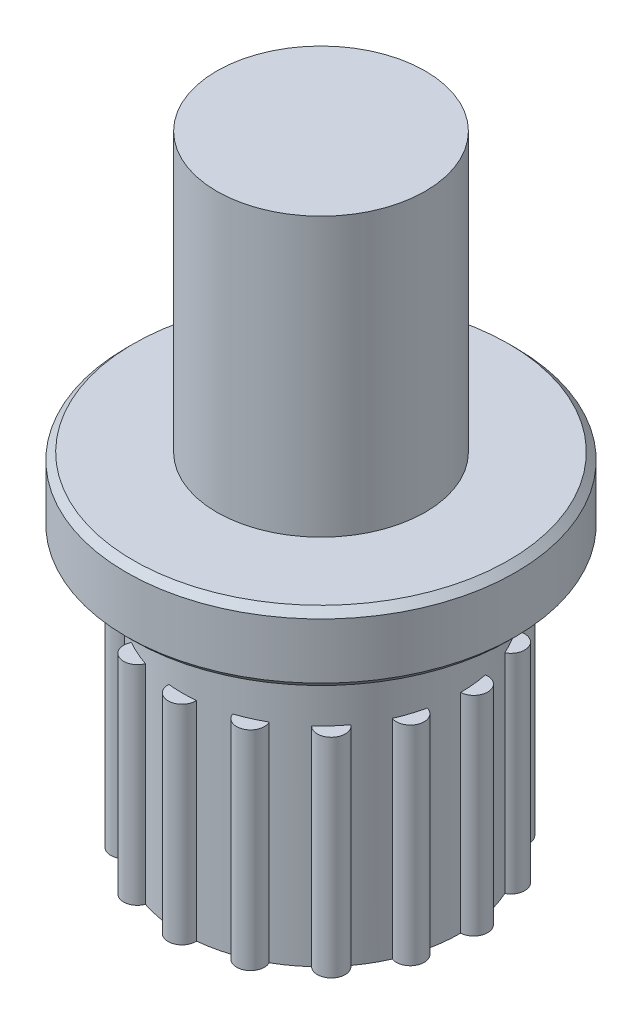
SolidWorks part; units mm, degrees
ref_plane "Front Plane" through (0, 0, 0) normal (0, 0, 1) x (1, 0, 0)
ref_plane "Top Plane" through (0, 0, 0) normal (0, 1, 0) x (1, 0, 0)
ref_plane "Right Plane" through (0, 0, 0) normal (1, 0, 0) x (0, 0, -1)
sketch "Sketch2" plane through (0, 0, 0) normal (1, 0, 0) x (0, 0, -1)
  line L0 (0, 0) -> (10, 0)
  line L1 (10, 0) -> (10, 20)
  line L2 (10, 20) -> (14, 20)
  line L3 (14, 20) -> (14, 25)
  line L4 (14, 25) -> (7.5, 25)
  line L5 (7.5, 25) -> (7.5, 45)
  line L6 (7.5, 45) -> (0, 45)
  line L7 (0, 45) -> (0, 0)
  dimension "D1" = 7.5
  dimension "D2" = 14
  dimension "D3" = 10
  dimension "D4" = 20
  dimension "D5" = 5
  dimension "D6" = 20
revolve "Revolve1" add sketch "Sketch2" angle 360 about L7
ref_axis "Axis1" through (0, 25, 0) along (0, 1, 0)
sketch "Sketch3" plane through (0, 0, 0) normal (0, -1, 0) x (1, 0, 0)
  circle A0 centre (0, 10) radius 1
  circle A1 centre (0, 0) radius 10 construction
  circle A2 centre (0, 0) radius 10 construction
  point P6 (0, 0)
  dimension "D1" = 2
extrude "Boss-Extrude1" add sketch "Sketch3" against normal offset from surface (15 mm away) 5 up to face at (0, 20, 14)
pattern_circular "CirPattern1" count 15 over 360 about axis through (0, 25, 0) along (0, 1, 0) of "Boss-Extrude1"
chamfer "Chamfer1" distance 0.5 angle 45 2 edges at (0, 25, 14) (0, 20, 14)
